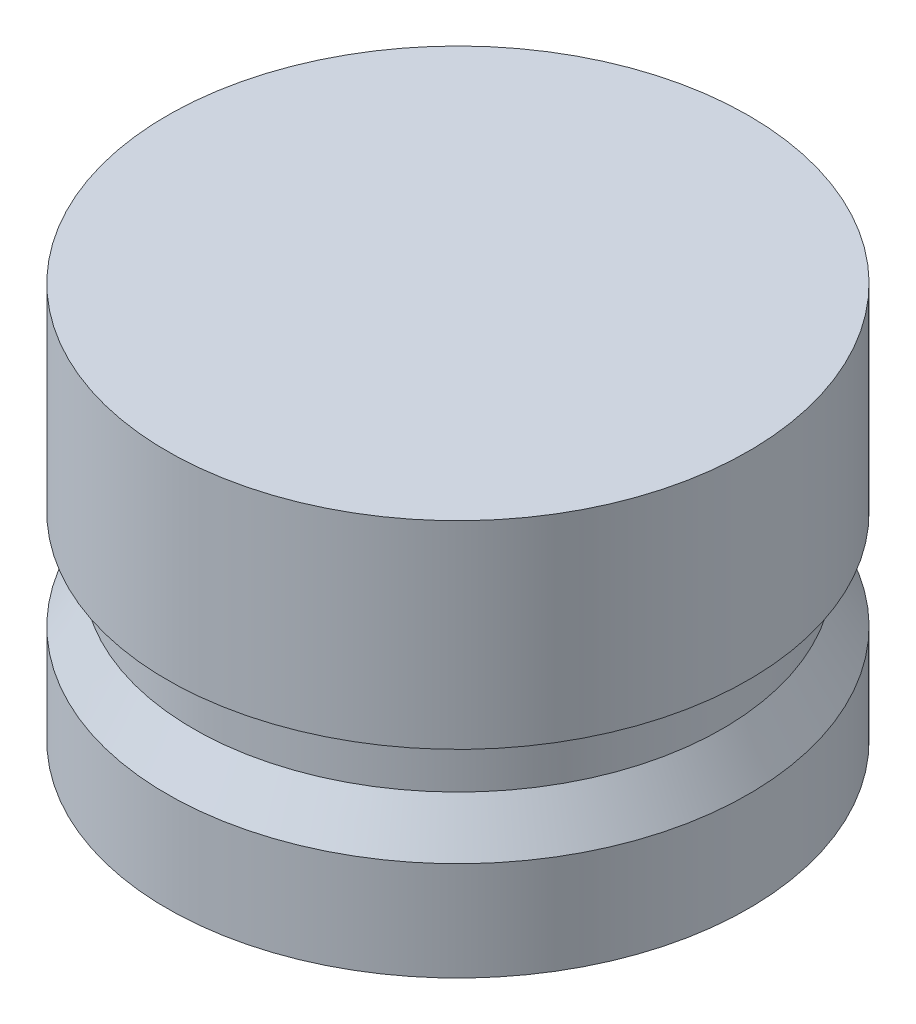
SolidWorks part; units mm, degrees
ref_plane "Front Plane" through (0, 0, 0) normal (0, 0, 1) x (1, 0, 0)
ref_plane "Top Plane" through (0, 0, 0) normal (0, 1, 0) x (1, 0, 0)
ref_plane "Right Plane" through (0, 0, 0) normal (1, 0, 0) x (0, 0, -1)
sketch "Sketch1" plane through (0, 0, 0) normal (0, 0, 1) x (1, 0, 0)
  line L0 (0, 0) -> (0, 12.7) construction
  line L1 (0, 0) -> (-9.3218, 0)
  line L2 (-9.3218, 0) -> (-9.3218, 3.175)
  line L4 (-8.4836, 4.572) -> (-8.4836, 6.35)
  line L5 (-8.4836, 6.35) -> (-9.3218, 6.35)
  line L6 (-9.3218, 6.35) -> (-9.3218, 12.7)
  line L7 (-9.3218, 12.7) -> (0, 12.7)
  line L8 (-9.525, 16.6801) -> (-9.525, -9.6051) construction
  line L9 (0, 0) -> (0, 12.7)
  line L10 (-8.4836, 4.572) -> (-9.3218, 3.175)
  dimension "D1" = 12.7
  dimension "D2" = 9.3218
  dimension "D3" = 1.778
  dimension "D4" = 3.175
  dimension "D5" = 9.525
  dimension "D6" = 8.4836
  dimension "D7" = 6.35
revolve "Revolve1" add sketch "Sketch1" angle 360 about L9
